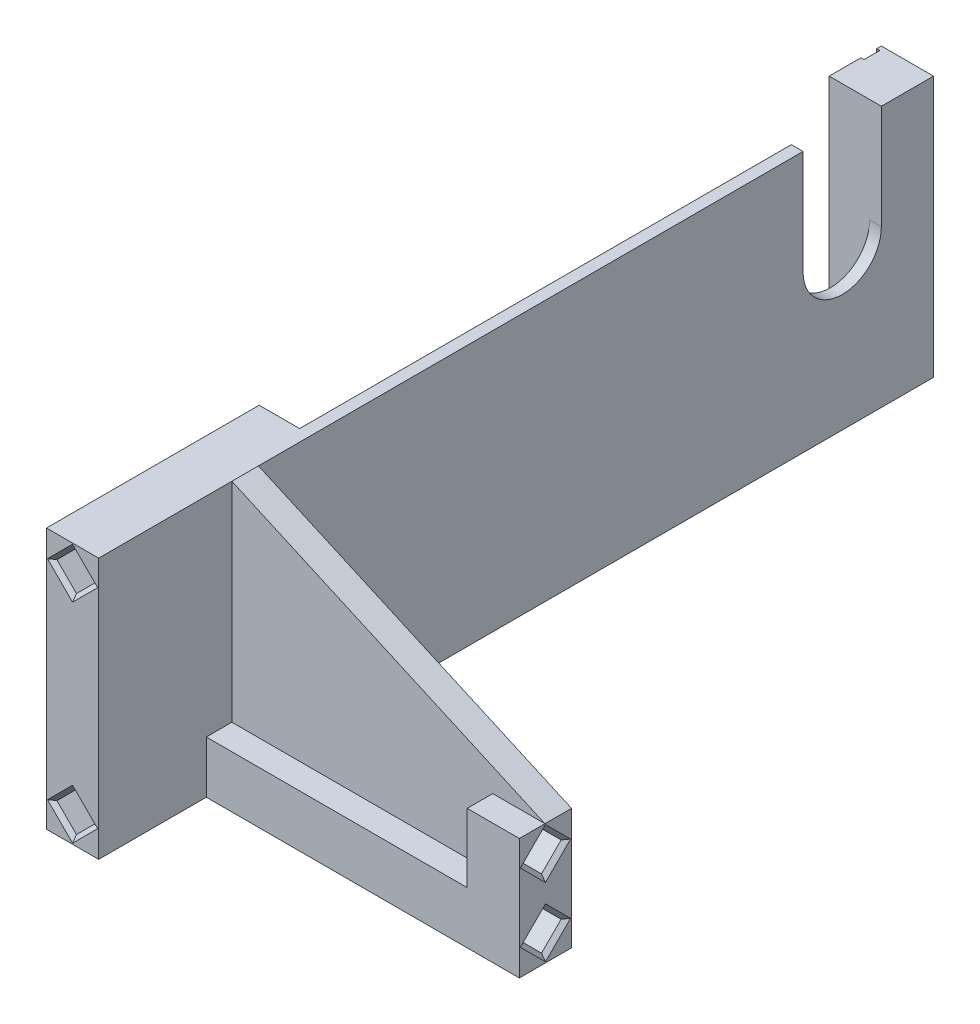
SolidWorks part; units mm, degrees
ref_plane "Front Plane" through (0, 0, 0) normal (0, 0, 1) x (1, 0, 0)
ref_plane "Top Plane" through (0, 0, 0) normal (0, 1, 0) x (1, 0, 0)
ref_plane "Right Plane" through (0, 0, 0) normal (1, 0, 0) x (0, 0, -1)
sketch "Sketch2" plane through (0, 0, 0) normal (0, 1, 0) x (1, 0, 0)
  line L0 (25.75, 56.5) -> (25.75, 62.5) construction
  line L1 (31.75, 62.5) -> (-31.75, 62.5) construction
  line L2 (31.75, 62.5) -> (31.75, -62.5) construction
  line L3 (31.75, -62.5) -> (-31.75, -62.5) construction
  line L4 (-31.75, 62.5) -> (-31.75, -62.5) construction
  line L5 (25.75, 56.5) -> (31.75, 56.5) construction
  line L6 (-25.75, -56.5) -> (-31.75, -56.5) construction
  line L7 (-25.75, -56.5) -> (-25.75, -62.5) construction
  point P4 (0, -56.5)
  point P5 (25.75, -56.5)
  point P6 (0, 56.5)
  point P8 (25.75, 56.5)
  point P12 (-25.75, -56.5)
  point P13 (0, -62.5)
  point P14 (-25.75, 56.5)
  point P17 (31.75, 0)
  dimension "D1" = 63.5
  dimension "D2" = 125
  dimension "D3" = 6
  dimension "D4" = 6
sketch "Sketch3" plane through (0, 0, 0) normal (0, 1, 0) x (1, 0, 0)
  line L0 (-31.75, 62.5) -> (-31.75, -62.5) construction
  line L1 (-29.21, 48.3067) -> (-37.6767, 48.3067)
  line L2 (-29.21, 48.3067) -> (-29.21, -61.23)
  line L3 (-29.21, -87.16) -> (-37.6767, -87.16)
  line L4 (-37.6767, 48.3067) -> (-37.6767, -87.16)
  line L6 (31.75, -62.5) -> (-31.75, -62.5) construction
  line L8 (-29.21, -61.23) -> (21.59, -61.23)
  line L10 (-29.21, -69.6967) -> (21.59, -69.6967)
  line L11 (21.59, -61.23) -> (21.59, -69.6967)
  line L13 (-29.21, -69.6967) -> (-29.21, -87.16)
  point P4 (-33.4433, 48.3067)
  dimension "D1" = 135.4667
  dimension "D2" = 8.4667
  dimension "D3" = 1.27
  dimension "D4" = 1.6933
  dimension "D5" = 50.8
  dimension "D6" = 17.4633
  dimension "D7" = 8.4667
extrude "Boss-Extrude2" add sketch "Sketch3" along normal blind 8.4667
sketch "Sketch12" plane through (0, 0, 0) normal (0, 1, 0) x (1, 0, 0)
  line L2 (-29.21, -61.23) -> (-29.21, 48.3067) construction
  line L5 (-25.75, -51.77) -> (-29.21, -51.77)
  line L6 (-25.75, -61.23) -> (-29.21, -61.23)
  line L7 (-29.21, -51.77) -> (-29.21, -61.23)
  line L8 (-25.75, -56.5) -> (-25.75, -62.5) construction
  line L9 (21.59, -61.23) -> (-29.21, -61.23) construction
  arc A1 (-25.75, -61.23) -> (-25.75, -51.77) centre (-25.75, -56.5) ccw
extrude "Boss-Extrude4" add sketch "Sketch12" along normal blind 3.175
sketch "Sketch14" plane through (0, 3.175, 0) normal (0, 1, 0) x (1, 0, 0)
  point P0 (-25.75, 56.5)
  point P1 (-25.75, -56.5)
hole_wizard "#24 (0.152) Diameter Hole1" positions "Sketch14" profile "Sketch15" hole size "#24" standard "ANSI Inch" end condition up to next
sketch "Sketch15" plane through (-25.75, 3.175, -56.5) normal (1, 0, 0) x (0, 0, 1)
  line L0 (0, 0) -> (0, 3.175)
  line L1 (0, 3.175) -> (1.9304, 3.175)
  line L2 (1.9304, 3.175) -> (1.9304, 0)
  line L5 (1.9304, 0) -> (0, 0)
  line L11 (0, -6.35) -> (0, 107.95) construction
  dimension "Thru Hole Dia." = 3.8608
  dimension "Thru Hole Depth" = 3.175
sketch "Sketch16" plane through (0, 8.4667, 0) normal (0, 1, 0) x (1, 0, 0)
  line L0 (-37.6767, -87.16) -> (-37.6767, -52.6472)
  line L1 (-29.21, -61.23) -> (-29.21, 48.3067) construction
  line L2 (-37.6767, 48.3067) -> (-29.21, 48.3067)
  line L5 (-37.6767, 39.84) -> (-31.115, 39.84)
  line L6 (-31.115, 39.84) -> (-31.115, -52.6472)
  line L7 (-31.115, -52.6472) -> (-37.6767, -52.6472)
  line L8 (-37.6767, 39.84) -> (-37.6767, 48.3067)
  line L9 (-29.21, -6.4617) -> (-31.115, -6.4617) construction
  line L11 (-37.6767, 48.3067) -> (-37.6767, -87.16) construction
  line L12 (-29.21, -87.16) -> (-37.6767, -87.16)
  line L13 (-29.21, -87.16) -> (-29.21, 48.3067)
  line L16 (-29.21, -61.23) -> (-29.21, 48.3067) construction
  dimension "D1" = 1.905
  dimension "D2" = 8.4667
extrude "Boss-Extrude5" add sketch "Sketch16" along normal blind 33.8667
sketch "Sketch19" plane through (0, 8.4667, 0) normal (0, 1, 0) x (1, 0, 0)
  line L0 (-29.21, -69.6967) -> (21.59, -69.6967) construction
  line L1 (21.59, -61.23) -> (13.1233, -61.23)
  line L2 (21.59, -61.23) -> (21.59, -69.6967)
  line L3 (21.59, -69.6967) -> (13.1233, -69.6967)
  line L4 (13.1233, -61.23) -> (13.1233, -69.6967)
extrude "Boss-Extrude7" add sketch "Sketch19" along normal blind 11.1417
sketch "Sketch18" plane through (0, 0, 61.23) normal (0, 0, -1) x (-1, 0, 0)
  line L0 (-21.59, 19.6083) -> (29.21, 42.3333)
  line L1 (-13.1233, 8.4667) -> (29.21, 8.4667) construction
  line L3 (29.21, 42.3333) -> (37.6767, 42.3333) construction
  line L4 (29.21, 42.3333) -> (29.21, 0) construction
  line L5 (29.21, 42.3333) -> (29.21, 8.4667)
  line L8 (-21.59, 19.6083) -> (-21.59, 0) construction
  line L9 (-21.59, 19.6083) -> (-13.1233, 19.6083)
  line L10 (-13.1233, 19.6083) -> (-13.1233, 8.4667)
  line L11 (-13.1233, 8.4667) -> (29.21, 8.4667)
extrude "Boss-Extrude6" add sketch "Sketch18" against normal blind 4.318
sketch "Sketch4" plane through (0, 0, 87.16) normal (0, 0, 1) x (1, 0, 0)
  line L0 (-36.6183, 4.2333) -> (-33.4433, 7.4083)
  line L1 (-36.6183, 4.2333) -> (-33.4433, 1.0583)
  line L2 (-33.4433, 7.4083) -> (-30.2683, 4.2333)
  line L3 (-33.4433, 1.0583) -> (-30.2683, 4.2333)
  line L4 (-36.6183, 4.2333) -> (-30.2683, 4.2333) construction
  line L5 (-33.4433, 7.4083) -> (-33.4433, 1.0583) construction
  line L6 (-37.6767, 8.4667) -> (-29.21, 8.4667) construction
  line L8 (-36.6183, 38.1) -> (-33.4433, 41.275)
  line L9 (-36.6183, 38.1) -> (-33.4433, 34.925)
  line L10 (-33.4433, 41.275) -> (-30.2683, 38.1)
  line L11 (-33.4433, 34.925) -> (-30.2683, 38.1)
  line L12 (-36.6183, 38.1) -> (-30.2683, 38.1) construction
  line L13 (-33.4433, 41.275) -> (-33.4433, 34.925) construction
  line L14 (-37.6767, 42.3333) -> (-29.21, 42.3333) construction
  line L15 (-37.6767, 0) -> (-29.21, 0) construction
  point P1 (-33.4433, 4.2333)
  point P3 (-33.4433, 8.4667)
  point P12 (-33.4433, 38.1)
  dimension "D1" = 6.35
  dimension "D2" = 4.2333
  dimension "D3" = 4.2333
extrude "RightPins" cut sketch "Sketch4" against normal blind 6.35
sketch "Sketch5" plane through (0, 0, -48.3067) normal (0, 0, -1) x (-1, 0, 0)
  line L0 (30.2683, 4.2333) -> (33.4433, 7.4083)
  line L1 (30.2683, 4.2333) -> (33.4433, 1.0583)
  line L2 (33.4433, 7.4083) -> (36.6183, 4.2333)
  line L3 (33.4433, 1.0583) -> (36.6183, 4.2333)
  line L4 (30.2683, 4.2333) -> (36.6183, 4.2333) construction
  line L5 (33.4433, 7.4083) -> (33.4433, 1.0583) construction
  line L6 (29.21, 8.4667) -> (37.6767, 8.4667) construction
  line L8 (29.21, 0) -> (37.6767, 0) construction
  line L9 (30.2683, 38.1) -> (33.4433, 41.275)
  line L10 (30.2683, 38.1) -> (33.4433, 34.925)
  line L11 (33.4433, 41.275) -> (36.6183, 38.1)
  line L12 (33.4433, 34.925) -> (36.6183, 38.1)
  line L13 (30.2683, 38.1) -> (36.6183, 38.1) construction
  line L14 (33.4433, 41.275) -> (33.4433, 34.925) construction
  line L16 (29.21, 42.3333) -> (37.6767, 42.3333) construction
  point P1 (33.4433, 4.2333)
  point P8 (33.4433, 8.4667)
  point P11 (33.4433, 38.1)
  dimension "D1" = 6.35
  dimension "D2" = 4.2333
  dimension "D3" = 4.2333
extrude "LeftPins" cut sketch "Sketch5" against normal blind 6.35
sketch "Sketch11" plane through (21.59, 0, 0) normal (1, 0, 0) x (0, 0, -1)
  line L0 (-68.6383, 4.2333) -> (-65.4633, 7.4083)
  line L1 (-68.6383, 4.2333) -> (-65.4633, 1.0583)
  line L2 (-65.4633, 7.4083) -> (-62.2883, 4.2333)
  line L3 (-65.4633, 1.0583) -> (-62.2883, 4.2333)
  line L4 (-68.6383, 4.2333) -> (-62.2883, 4.2333) construction
  line L5 (-65.4633, 7.4083) -> (-65.4633, 1.0583) construction
  line L6 (-69.6967, 8.4667) -> (-61.23, 8.4667) construction
  line L7 (-68.6383, 15.375) -> (-65.4633, 18.55)
  line L8 (-69.6967, 0) -> (-61.23, 0) construction
  line L9 (-68.6383, 15.375) -> (-65.4633, 12.2)
  line L10 (-65.4633, 18.55) -> (-62.2883, 15.375)
  line L11 (-65.4633, 12.2) -> (-62.2883, 15.375)
  line L12 (-68.6383, 15.375) -> (-62.2883, 15.375) construction
  line L13 (-65.4633, 18.55) -> (-65.4633, 12.2) construction
  line L14 (-69.6967, 19.6083) -> (-65.548, 19.6083) construction
  point P1 (-65.4633, 4.2333)
  point P3 (-65.4633, 8.4667)
  point P11 (-65.4633, 15.375)
  dimension "D1" = 6.35
  dimension "D2" = 4.2333
  dimension "D3" = 4.2333
extrude "FrontPins" cut sketch "Sketch11" against normal blind 6.35
chamfer "PinChamfer" distance 0.635 angle 45 48 edges at (-35.0308, 5.8208, -48.3067) (-31.8558, 5.8208, -48.3067) (-31.8558, 2.6458, -48.3067) (-35.0308, 2.6458, -48.3067) (-31.8558, 5.8208, -41.9567) (-35.0308, 5.8208, -41.9567) (-35.0308, 2.6458, -41.9567) (-31.8558, 2.6458, -41.9567) (-35.0308, 5.8208, 80.81) (-31.8558, 5.8208, 80.81) (-31.8558, 2.6458, 80.81) (-35.0308, 2.6458, 80.81) (-31.8558, 5.8208, 87.16) (-35.0308, 5.8208, 87.16) (-35.0308, 2.6458, 87.16) (-31.8558, 2.6458, 87.16) (15.24, 5.8208, 67.0508) (15.24, 5.8208, 63.8758) (15.24, 2.6458, 63.8758) (15.24, 2.6458, 67.0508) (21.59, 2.6458, 67.0508) (21.59, 2.6458, 63.8758) (21.59, 5.8208, 63.8758) (21.59, 5.8208, 67.0508) (-31.8558, 39.6875, -41.9567) (-35.0308, 39.6875, -41.9567) (-35.0308, 36.5125, -41.9567) (-31.8558, 36.5125, -41.9567) (-35.0308, 39.6875, 80.81) (-31.8558, 39.6875, 80.81) (-31.8558, 36.5125, 80.81) (-35.0308, 36.5125, 80.81) (-35.0308, 39.6875, -48.3067) (-35.0308, 36.5125, -48.3067) (-31.8558, 36.5125, -48.3067) (-31.8558, 39.6875, -48.3067) (-31.8558, 39.6875, 87.16) (-31.8558, 36.5125, 87.16) (-35.0308, 36.5125, 87.16) (-35.0308, 39.6875, 87.16) (15.24, 16.9625, 67.0508) (15.24, 16.9625, 63.8758) (15.24, 13.7875, 63.8758) (15.24, 13.7875, 67.0508) (21.59, 16.9625, 63.8758) (21.59, 13.7875, 63.8758) (21.59, 13.7875, 67.0508) (21.59, 16.9625, 67.0508)
sketch "Sketch20" plane through (-29.21, 0, 0) normal (1, 0, 0) x (0, 0, -1)
  line L0 (39.84, 42.3333) -> (39.84, 8.4667) construction
  line L1 (39.84, 25.4) -> (39.84, 42.3333)
  line L2 (-61.23, 42.3333) -> (48.3067, 42.3333) construction
  line L3 (39.84, 42.3333) -> (27.14, 42.3333)
  line L4 (27.14, 42.3333) -> (27.14, 25.4)
  line L6 (62.5, 0) -> (-62.5, 0) construction
  arc A0 (27.14, 25.4) -> (39.84, 25.4) centre (33.49, 25.4) ccw
  dimension "D1" = 6.35
  dimension "D2" = 25.4
extrude "Cut-Extrude1" cut sketch "Sketch20" against normal up to next
sketch "Sketch21" plane through (0, 42.3333, 0) normal (0, 1, 0) x (1, 0, 0)
  line L0 (-37.6767, 48.3067) -> (-37.6767, 39.84) construction
  line L1 (-37.6767, 47.5447) -> (-37.1687, 47.5447)
  line L2 (-37.6767, 47.5447) -> (-37.6767, 45.0047)
  line L3 (-37.6767, 45.0047) -> (-37.1687, 45.0047)
  line L4 (-37.1687, 47.5447) -> (-37.1687, 45.0047)
  line L5 (-29.21, 48.3067) -> (-37.6767, 48.3067) construction
  dimension "D1" = 0.762
  dimension "D2" = 2.54
  dimension "D3" = 0.508
extrude "Cut-Extrude2" cut sketch "Sketch21" against normal up to next
